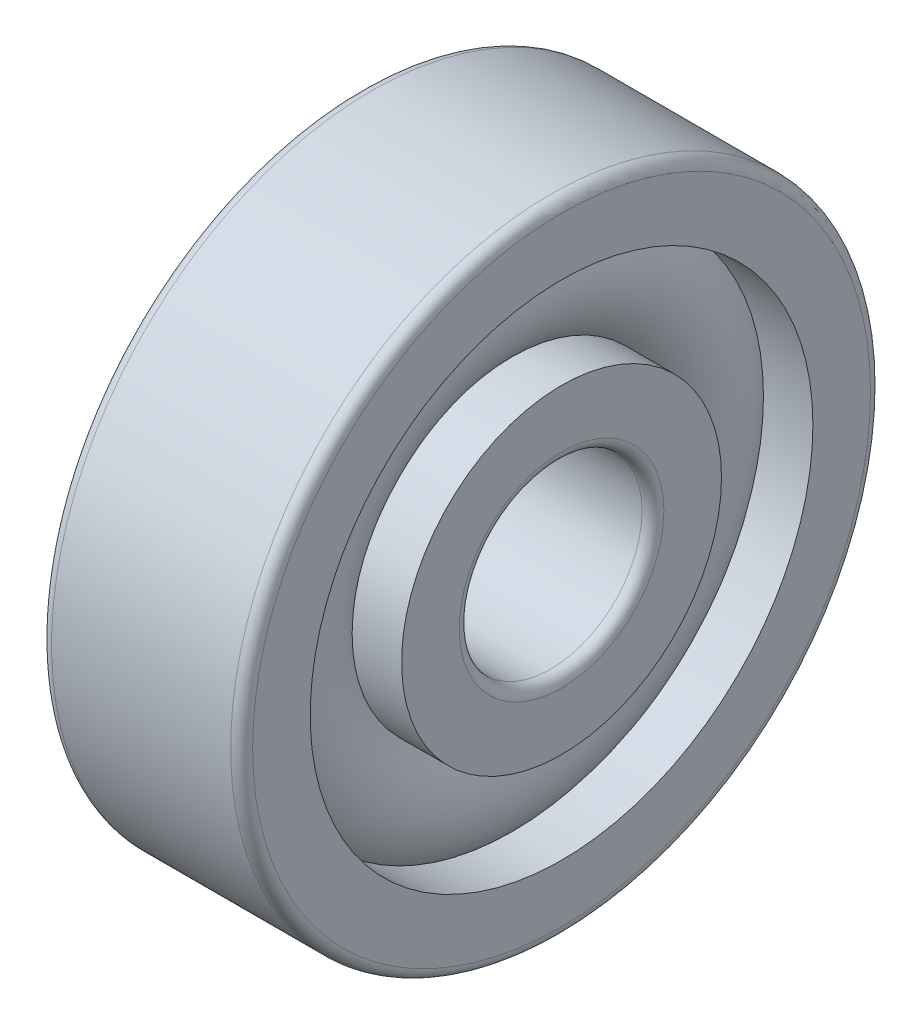
SolidWorks part; units mm, degrees
ref_plane "Plane1" through (0, 0, 0) normal (0, 0, 1) x (1, 0, 0)
ref_plane "Plane2" through (0, 0, 0) normal (0, 1, 0) x (1, 0, 0)
ref_plane "Plane3" through (0, 0, 0) normal (1, 0, 0) x (0, 0, -1)
sketch "Clipboard" plane through (0, 0, 0) normal (0, 0, 1) x (1, 0, 0)
  line L0 (-10, 0) -> (10, 0) construction
  line L1 (0, 0) -> (22.3471, -0.7804)
  line L2 (0, 0) -> (11.2431, 0.3926)
  line L3 (0, 0) -> (22.3471, -0.7804)
  line L4 (0, 0) -> (-22.3573, -0.3902)
  dimension "BallCLRad" = 11.25
sketch "CagSpiSke" plane through (0, 0, 0) normal (0, 0, 1) x (1, 0, 0)
  line L0 (0.375, 10.625) -> (0.375, 11.875)
  line L1 (0.375, 11.875) -> (-0.375, 11.875)
  line L2 (-0.375, 11.875) -> (-0.375, 10.625)
  line L3 (-0.375, 10.625) -> (0.375, 10.625)
  line L4 (-20.6375, 0) -> (20.6375, 0) construction
  line L5 (0, 0) -> (0, 23.7692) construction
  dimension "OD" = 23.75
  dimension "ID" = 21.25
revolve "CageSpine" add sketch "CagSpiSke" angle 0.001 about L4 reverse direction yes
ref_axis "Axis1" through (-50, 0, 0) along (1, 0, 0)
sketch "CagBalSke" plane through (0, 0, 0) normal (0, 0, 1) x (1, 0, 0)
  line L0 (-4.125, 11.25) -> (4.125, 11.25)
  line L1 (-1.905, 11.25) -> (1.905, 11.25) construction
  line L2 (-10, 0) -> (10, 0) construction
  line L3 (0, 0) -> (0, 24) construction
  arc A0 (4.125, 11.25) -> (-4.125, 11.25) centre (0, 11.25) cw
  dimension "BallCLRad" = 11.25
revolve "CageBall" [suppressed] add sketch "CagBalSke" angle 360 about L1 reverse direction yes
pattern_circular "CageBalls" [suppressed] count 2 every 180 about axis through (-50, 0, 0) along (1, 0, 0)
sketch "CagTrmODSke" plane through (0, 0, 0) normal (0, 0, 1) x (1, 0, 0)
  line L0 (4.126, 11.875) -> (4.126, 15.376)
  line L1 (4.126, 15.376) -> (-4.126, 15.376)
  line L2 (-4.126, 15.376) -> (-4.126, 11.875)
  line L3 (-4.126, 11.875) -> (4.126, 11.875)
  line L4 (-20.6375, 0) -> (20.6375, 0) construction
  line L5 (0, 0) -> (0, 25) construction
  dimension "Width" = 8.252
  dimension "ID" = 23.75
  dimension "OD" = 30.752
revolve "CageTrimOD" [suppressed] cut sketch "CagTrmODSke" angle 360 about L4 reverse direction yes
sketch "CagTrmIDSke" plane through (0, 0, 0) normal (0, 0, 1) x (1, 0, 0)
  line L0 (4.126, 7.126) -> (4.126, 10.625)
  line L1 (4.126, 10.625) -> (-4.126, 10.625)
  line L2 (-4.126, 10.625) -> (-4.126, 7.126)
  line L3 (-4.126, 7.126) -> (4.126, 7.126)
  line L4 (-20.6375, 0) -> (20.6375, 0) construction
  line L5 (0, 0) -> (0, 25) construction
  dimension "Width" = 8.252
  dimension "ID" = 14.252
  dimension "OD" = 21.25
revolve "CageTrimID" [suppressed] cut sketch "CagTrmIDSke" angle 360 about L4 reverse direction yes
sketch "BalSimSke" plane through (0, 0, 0) normal (0, 0, 1) x (1, 0, 0)
  line L0 (-10, 0) -> (10, 0) construction
  line L1 (-10, 11.25) -> (10, 11.25) construction
  line L2 (0, 0) -> (0, 23) construction
  circle A0 centre (0, 11.25) radius 3.75
  dimension "BallCLRad" = 11.25
  dimension "Ball_diameter" = 7.5
revolve "BallsSimplified" add sketch "BalSimSke" angle 360 about L0
sketch "BalDetSke" plane through (0, 0, 0) normal (0, 0, 1) x (1, 0, 0)
  line L0 (-3.75, 11.25) -> (3.75, 11.25)
  line L1 (-1.905, 11.25) -> (1.905, 11.25) construction
  line L2 (0, 0) -> (0, 25) construction
  arc A0 (3.75, 11.25) -> (-3.75, 11.25) centre (0, 11.25) cw
  dimension "BallCLRad" = 11.25
  dimension "Ball_diameter" = 7.5
revolve "BallDetailed" [suppressed] add sketch "BalDetSke" angle 360 about L1 reverse direction yes
sketch "InnRacSke" plane through (0, 0, 0) normal (0, 0, 1) x (1, 0, 0)
  line L0 (-2.7615, 8.75) -> (-5.5, 8.75)
  line L1 (-5.5, 8.75) -> (-5.5, 5.6)
  line L2 (-4.9, 5) -> (4.9, 5)
  line L3 (5.5, 5.6) -> (5.5, 8.75)
  line L4 (5.5, 8.75) -> (2.7615, 8.75)
  line L5 (-20.6375, 0) -> (20.6375, 0) construction
  line L6 (0, 0) -> (0, 30) construction
  arc A0 (-5.5, 5.6) -> (-4.9, 5) centre (-4.9, 5.6) ccw
  arc A1 (4.9, 5) -> (5.5, 5.6) centre (4.9, 5.6) ccw
  arc A2 (2.7615, 8.75) -> (-2.7615, 8.75) centre (0, 11.25) cw
  dimension "BallCLRad" = 11.25
  dimension "Fillet_radius" = 0.6
  dimension "Ball_diameter" = 7.45
  dimension "ID" = 10
  dimension "OD" = 17.5
  dimension "Width" = 11
revolve "InnerRace" add sketch "InnRacSke" angle 360 about L5 reverse direction yes
sketch "OutRacSke" plane through (0, 0, 0) normal (0, 0, 1) x (1, 0, 0)
  line L0 (-2.7615, 13.75) -> (-5.5, 13.75)
  line L1 (-5.5, 13.75) -> (-5.5, 16.9)
  line L2 (-4.9, 17.5) -> (4.9, 17.5)
  line L3 (5.5, 16.9) -> (5.5, 13.75)
  line L4 (5.5, 13.75) -> (2.7615, 13.75)
  line L5 (-20.6375, 0) -> (20.6375, 0) construction
  line L6 (0, 0) -> (0, 30) construction
  arc A0 (-5.5, 16.9) -> (-4.9, 17.5) centre (-4.9, 16.9) cw
  arc A1 (4.9, 17.5) -> (5.5, 16.9) centre (4.9, 16.9) cw
  arc A2 (2.7615, 13.75) -> (-2.7615, 13.75) centre (0, 11.25) ccw
  dimension "BallCLRad" = 11.25
  dimension "Fillet_radius" = 0.6
  dimension "Ball_diameter" = 7.45
  dimension "Width" = 11
revolve "OuterRace" add sketch "OutRacSke" angle 360 about L5 reverse direction yes
pattern_circular "BallsDetailed" [suppressed] count 2 every 180 about axis through (-50, 0, 0) along (1, 0, 0)
equation "\"BallCLRad@Clipboard\" = ( \"OD@OutRacSke\" + \"ID@InnRacSke\" ) / 4"
equation "\"BallCLRad@BalSimSke\" = \"BallCLRad@Clipboard\""
equation "\"BallCLRad@BalDetSke\" = \"BallCLRad@Clipboard\""
equation "\"BallCLRad@InnRacSke\" = \"BallCLRad@Clipboard\""
equation "\"BallCLRad@OutRacSke\" = \"BallCLRad@Clipboard\""
equation "\"Ball_diameter@InnRacSke\" = \"Ball_diameter@BalDetSke\" - 0.05"
equation "\"Ball_diameter@OutRacSke\" = \"Ball_diameter@BalDetSke\" - 0.05"
equation "\"Ball_diameter@BalSimSke\" = \"Ball_diameter@BalDetSke\""
equation "\"Width@OutRacSke\" = \"Width@InnRacSke\""
equation "\"Fillet_radius@OutRacSke\" = \"Fillet_radius@InnRacSke\""
equation "\"Max_count@Clipboard\" = int( 3.14159265 / atn(( \"Ball_diameter@BalDetSke\" / 2) / sqr( \"BallCLRad@Clipboard\"  *  \"BallCLRad@Clipboard\" - ( \"Ball_diameter@BalDetSke\" / 2) *  ( \"Ball_diameter@BalDetSke\" / 2))))"
equation "\"Max_count@Clipboard\" = ((sgn( \"Max_count@Clipboard\" - \"Count@Clipboard\" )-1)*( \"Max_count@Clipboard\" - \"Count@Clipboard\" ))/-2+ \"Count@Clipboard\""
equation "\"Count@BallsDetailed\" = int( \"Show_count@Clipboard\" ) "
equation "\"Count@BallsDetailed\" = ((sgn( \"Count@BallsDetailed\" - \"Max_count@Clipboard\" )-1)*( \"Count@BallsDetailed\" - \"Max_count@Clipboard\" ))/-2+ \"Max_count@Clipboard\""
equation "\"Count@BallsDetailed\" = ((sgn( \"Count@BallsDetailed\" - \"Min_count@Clipboard\" )+1)*( \"Count@BallsDetailed\" - \"Min_count@Clipboard\"))/2 +\"Min_count@Clipboard\""
equation "\"Angle@BallsDetailed\" = 360.0 / \"Max_count@Clipboard\""
equation "\"BallCLRad@CagBalSke\" = \"BallCLRad@Clipboard\""
equation "\"Count@CageBalls\" = \"Count@BallsDetailed\""
equation "\"Angle@CageBalls\" = \"Angle@BallsDetailed\""
equation "\"Angle@CageSpine\" =  \"Angle@CageBalls\" * ( \"Count@CageBalls\" -1 + int( \"Count@CageBalls\" / \"Max_count@Clipboard\" ) )  + 0.001 -  int( \"Count@CageBalls\" / \"Max_count@Clipboard\" ) * 0.001"
equation "\"Angle@CageSpine\" =  \"Angle@CageSpine\" * int( \"Min_count@Clipboard\" / 2) + int(1 / \"Min_count@Clipboard\")  * 0.001"
equation "\"CageWallOD@CagBalSke\" =  \"Ball_diameter@BalDetSke\" * 1.1"
equation "\"Thickness@CagSpiSke\" =  \"Ball_diameter@BalDetSke\" * 0.1"
equation "\"OD@CagTrmODSke\" = \"BallCLRad@Clipboard\" * 2 + \"CageWallOD@CagBalSke\" + 0.002"
equation "\"ID@CagTrmODSke\" = \"BallCLRad@Clipboard\" * 2 + \"Ball_diameter@BalDetSke\" / 6"
equation "\"OD@CagTrmIDSke\" = \"BallCLRad@Clipboard\" * 2 - \"Ball_diameter@BalDetSke\" / 6"
equation "\"ID@CagTrmIDSke\" = \"BallCLRad@Clipboard\" * 2 - \"CageWallOD@CagBalSke\" + 0.002"
equation "\"OD@CagSpiSke\" = \"ID@CagTrmODSke\""
equation "\"ID@CagSpiSke\" = \"OD@CagTrmIDSke\""
equation "\"Width@CagTrmODSke\" = \"CageWallOD@CagBalSke\" + 0.002"
equation "\"Width@CagTrmIDSke\" = \"CageWallOD@CagBalSke\" + 0.002"
